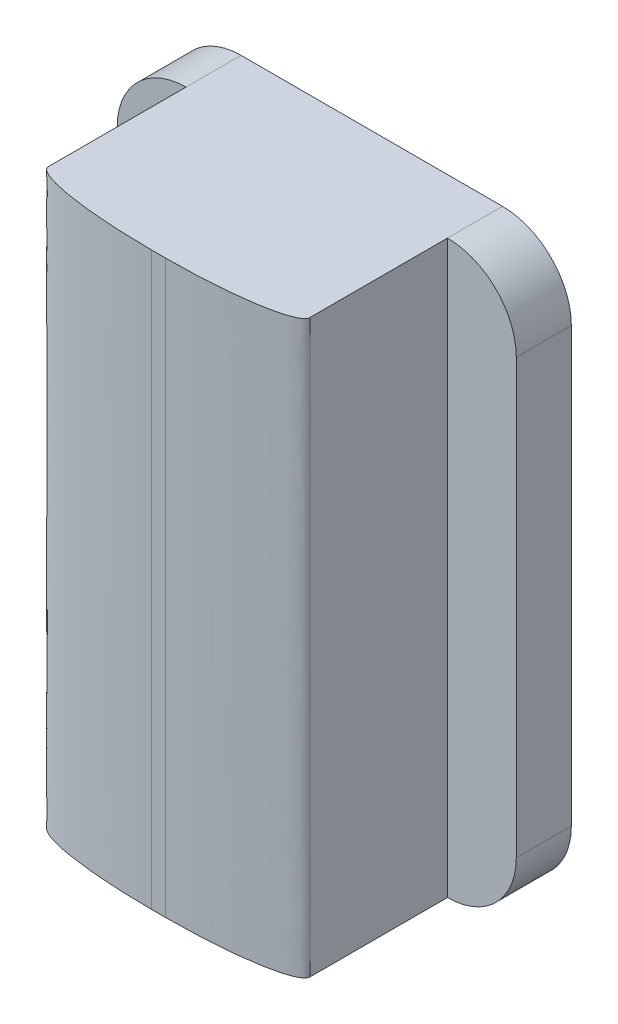
SolidWorks part; units mm, degrees
ref_plane "Front" through (0, 0, 0) normal (0, 0, 1) x (1, 0, 0)
ref_plane "Top" through (0, 0, 0) normal (0, 1, 0) x (1, 0, 0)
ref_plane "Right" through (0, 0, 0) normal (1, 0, 0) x (0, 0, -1)
sketch "草图1" plane through (0, 0, 0) normal (0, 0, 1) x (1, 0, 0)
  line L0 (0.6, -78.273) -> (0.6, -61.673) construction
  line L1 (-1.3, -78.273) -> (-1.3, -61.673)
  line L2 (2.5, -78.273) -> (2.5, -61.673)
  arc A0 (-1.3, -78.273) -> (2.5, -78.273) centre (0.6, -78.273) ccw
  arc A1 (2.5, -61.673) -> (-1.3, -61.673) centre (0.6, -61.673) ccw
  point P4 (0.6, -69.973)
  dimension "D1" = 3.8
extrude "凸台-拉伸1" add sketch "草图1" along normal blind 3.1
sketch "草图2" plane through (0, 0, 0) normal (0, 0, -1) x (-1, 0, 0)
  line L8 (2.3, -78.273) -> (2.3, -61.673)
  line L9 (-3.5, -61.673) -> (-3.5, -78.273)
  line L10 (2.3, -78.273) -> (2.3, -61.673)
  line L11 (-3.5, -61.673) -> (-3.5, -78.273)
  arc A8 (-3.5, -78.273) -> (2.3, -78.273) centre (-0.6, -78.273) ccw
  arc A9 (2.3, -61.673) -> (-3.5, -61.673) centre (-0.6, -61.673) ccw
  arc A10 (-3.5, -78.273) -> (2.3, -78.273) centre (-0.6, -78.273) ccw
  arc A11 (2.3, -61.673) -> (-3.5, -61.673) centre (-0.6, -61.673) ccw
  dimension "D1" = 1
extrude "凸台-拉伸2" add sketch "草图2" against normal blind 0.8
ref_plane "基准面1" through (0, 0, 3.1) normal (0, 0, 1) x (1, 0, 0)
fillet "圆角1" radius 0.3 4 edges at (2.5, -69.973, 3.1) (0.6, -59.773, 3.1) (0.6, -80.173, 3.1) (-1.3, -69.973, 3.1) second distance 1.8 first distance on face at (2.5, -69.973, 1.95) first distance on face at (0.6, -60.723, 1.95) first distance on face at (0.6, -79.223, 1.95) first distance on face at (-1.3, -69.973, 1.95)
sketch "草图3" plane through (0, 0, 0) normal (0, 0, -1) x (-1, 0, 0)
  line L0 (-0.6, -61.673) -> (-0.6, -78.273) construction
  circle A0 centre (-0.6, -61.673) radius 1
  circle A1 centre (-0.6, -69.973) radius 1.0967
  circle A2 centre (-0.6, -78.273) radius 1.0967
  point P9 (-0.6, -69.973)
  dimension "D1" = 2
extrude "凸台-拉伸3" add sketch "草图3" along normal blind 1.05
sketch "草图6" plane through (0, 0, 0) normal (0, 0, -1) x (-1, 0, 0)
  line L0 (-0.6, -78.273) -> (-0.6, -69.973) construction
  line L1 (-0.6, -69.973) -> (-0.6, -61.673) construction
  line L2 (-3.5, -61.673) -> (-3.5, -78.273) construction
  line L3 (2.3, -75.273) -> (-3.5, -75.273)
  line L4 (2.3, -75.273) -> (2.3, -72.973)
  line L5 (2.3, -72.973) -> (-3.5, -72.973)
  line L6 (-3.5, -75.273) -> (-3.5, -72.973)
  line L7 (2.3, -75.273) -> (-3.5, -72.973) construction
  line L8 (2.3, -72.973) -> (-3.5, -75.273) construction
  line L10 (2.3, -66.973) -> (-3.5, -66.973)
  line L11 (2.3, -66.973) -> (2.3, -64.673)
  line L12 (2.3, -64.673) -> (-3.5, -64.673)
  line L13 (-3.5, -66.973) -> (-3.5, -64.673)
  line L14 (2.3, -66.973) -> (-3.5, -64.673) construction
  line L15 (2.3, -64.673) -> (-3.5, -66.973) construction
  point P4 (-0.6, -74.123)
  point P13 (-0.6, -65.823)
  dimension "D1" = 2.3
fillet "圆角5" radius 0.9 3 edges at (1.6, -61.673, 0) (1.6967, -69.973, 0) (1.6967, -78.273, 0)
sketch "草图5" [suppressed] plane through (0, 0, 3.1) normal (0, 0, 1) x (1, 0, 0)
  line L0 (1.801, -60.7382) -> (1.801, -79.2175) construction
  text T1 "OldGerman" font "DS ISO 1" height 2.6
sketch "草图7" plane through (0, 0, 0) normal (0, 0, -1) x (-1, 0, 0)
  line L0 (-3.5, -66.973) -> (-3.5, -64.673) construction
  line L1 (2.3, -74.123) -> (-3.5, -74.123)
  line L2 (2.3, -74.123) -> (2.3, -65.823)
  line L3 (2.3, -65.823) -> (-3.5, -65.823)
  line L4 (-3.5, -74.123) -> (-3.5, -65.823)
  line L5 (2.3, -74.123) -> (-3.5, -65.823) construction
  line L6 (2.3, -65.823) -> (-3.5, -74.123) construction
  line L7 (12.3, -84.123) -> (12.3, -55.823)
  line L8 (12.3, -55.823) -> (-13.5, -55.823)
  line L9 (-13.5, -84.123) -> (-13.5, -55.823)
  line L10 (12.3, -84.123) -> (-13.5, -84.123)
  point P0 (-0.6, -69.973)
  dimension "D1" = 10
extrude "切除-拉伸2" cut sketch "草图7" against normal through all and the other way through all
fillet "圆角6" radius 1 4 edges at (3.5, -74.123, 0.4) (3.5, -65.823, 0.4) (-2.3, -65.823, 0.4) (-2.3, -74.123, 0.4)
